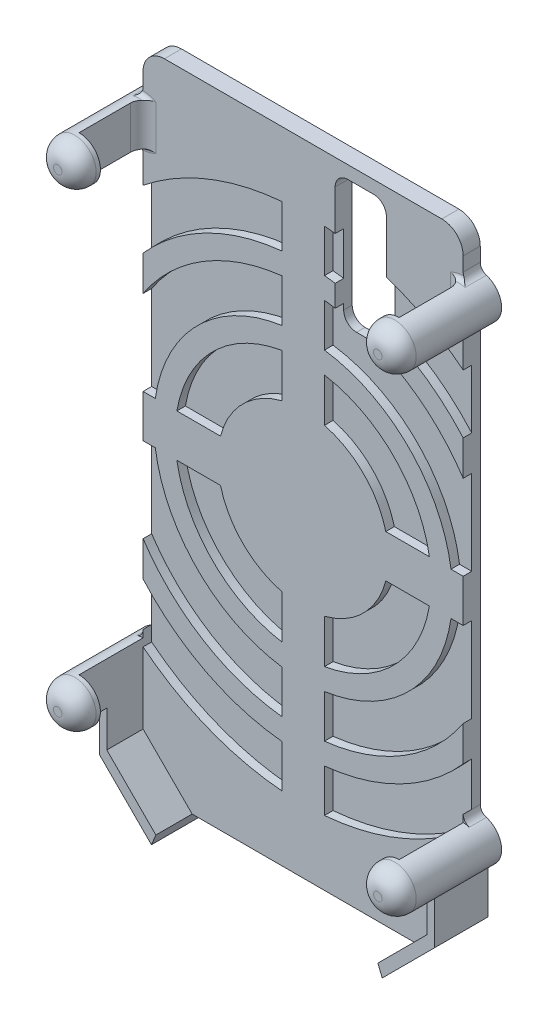
SolidWorks part; units mm, degrees
ref_plane "Front Plane" through (0, 0, 0) normal (0, 0, 1) x (1, 0, 0)
ref_plane "Top Plane" through (0, 0, 0) normal (0, 1, 0) x (1, 0, 0)
ref_plane "Right Plane" through (0, 0, 0) normal (1, 0, 0) x (0, 0, -1)
sketch "Sketch1" plane through (0, 0, 0) normal (0, 0, 1) x (1, 0, 0)
  line L0 (-925, 75) -> (49075, 75) construction
  line L1 (11.5, 0) -> (63.5, 0)
  line L2 (0, 11.5) -> (0, 20)
  line L3 (0, 150) -> (75, 150)
  line L4 (75, 11.5) -> (75, 20)
  line L5 (37.5, -1000) -> (37.5, 49000) construction
  line L6 (63.5, -1000) -> (63.5, 49000) construction
  line L7 (11.5, -1000) -> (11.5, 49000) construction
  line L8 (-643.6068, -707.1068) -> (34711.7323, 34648.2323) construction
  line L9 (718.6068, -707.1068) -> (-34636.7323, 34648.2323) construction
  line L10 (63.5, 0) -> (75, 11.5)
  line L11 (11.5, 0) -> (0, 11.5)
  line L12 (75, 140) -> (75, 150)
  line L13 (0, 140) -> (0, 150)
  line L14 (0, 30) -> (0, 130)
  line L15 (75, 30) -> (75, 130)
  line L16 (64.5355, -2.5) -> (76.7678, 9.7322)
  line L18 (10.4645, -2.5) -> (-1.7678, 9.7322)
  line L19 (-1.7678, 9.7322) -> (-1.7678, 20.3229)
  line L20 (76.7678, 9.7322) -> (76.7678, 20.3229)
  line L21 (11.5, 0) -> (10.4645, -2.5)
  line L22 (63.5, 0) -> (64.5355, -2.5)
  line L24 (10.4645, -2.5) -> (64.5355, -2.5) construction
  circle A0 centre (0, 135) radius 5
  circle A1 centre (75, 135) radius 5
  circle A2 centre (75, 25) radius 5
  circle A3 centre (0, 25) radius 5
  dimension "D5" = 25
  dimension "D7" = 15
  dimension "D1" = 2.5
  dimension "D2" = 130
  dimension "D3" = 26
  dimension "D4" = 26
  dimension "D6" = 25
extrude "Boss-Extrude1" add sketch "Sketch1" along normal blind 4 contours L14 A3 L2 L11 L1 L10 L4 A2 L15 A1 L12 L3 L13 A0 region at (37.5, 75.787, 0)
extrude "Boss-Extrude2" add sketch "Sketch1<3>" along normal blind 24 contours A3 | A0 | A1 | A2 region at (0, 25, 0) region at (75, 25, 0) region at (75, 135, 0) region at (0, 135, 0)
sketch "Sketch1<3>" plane through (0, 0, 0) normal (0, 0, 1) x (1, 0, 0) same geometry as "Sketch1"
extrude "Boss-Extrude3" add sketch "Sketch1<4>" along normal blind 12.5 contours L2 A3 L19 L18 L16 L20 A2 L4 L10 L1 L11 | L2 A3 L19 L18 L21 L11 region at (3.34, 7.7217, 0) region at (71.66, 7.7217, 0)
sketch "Sketch1<4>" plane through (0, 0, 0) normal (0, 0, 1) x (1, 0, 0) same geometry as "Sketch1"
ref_plane "Plane1" through (0, 150, 0) normal (0, 1, 0) x (1, 0, 0)
sketch "Sketch2" plane through (0, 150, 0) normal (0, 1, 0) x (1, 0, 0)
  line L1 (75, -4) -> (0, -4)
  line L2 (75, -4) -> (75, -19)
  line L3 (75, -19) -> (0, -19)
  line L4 (0, -4) -> (0, -19)
  dimension "D1" = 15
  dimension "D2" = 75
extrude "Cut-Extrude1" cut sketch "Sketch2" against normal blind 130
fillet "Fillet1" radius 4 4 edges at (80, 25, 24) (5, 25, 24) (5, 135, 24) (80, 135, 24)
fillet "Fillet2" radius 5 2 edges at (0, 150, 2) (75, 150, 2)
fillet "Fillet3" radius 2 6 edges at (75, 30, 2) (0, 30, 2) (0, 130, 2) (0, 140, 2) (75, 130, 2) (75, 140, 2)
ref_plane "Plane2" through (0, 0, 0) normal (0, 0, -1) x (-1, 0, 0)
sketch "Sketch3" plane through (0, 0, 0) normal (0, 0, -1) x (-1, 0, 0)
  line L0 (-45, -884.4947) -> (-45, 49115.5053) construction
  line L1 (-57, -886.6069) -> (-57, 49113.3931) construction
  line L2 (-1043.6831, 115) -> (48956.3169, 115) construction
  line L4 (14.1321, 150) -> (-14.1321, 150) construction
  line L5 (-1041.9112, 147) -> (48958.0888, 147) construction
  line L6 (-75, 31.7082) -> (-75, 128.2918) construction
  line L7 (-54, 147) -> (-48, 147)
  line L8 (-57, 144) -> (-57, 118)
  line L9 (-54, 115) -> (-48, 115)
  line L10 (-45, 144) -> (-45, 118)
  arc A0 (-48, 147) -> (-45, 144) centre (-48, 144) cw
  arc A1 (-54, 147) -> (-57, 144) centre (-54, 144) ccw
  arc A2 (-54, 115) -> (-57, 118) centre (-54, 118) cw
  arc A3 (-48, 115) -> (-45, 118) centre (-48, 118) ccw
  point P20 (-57, 147)
  point P25 (-45, 115)
  dimension "D5" = 3
  dimension "D1" = 18
  dimension "D2" = 12
  dimension "D3" = 35
  dimension "D4" = 3
extrude "Cut-Extrude3" cut sketch "Sketch3" against normal through all
ref_plane "Plane3" through (0, 0, 4) normal (0, 0, 1) x (1, 0, 0)
sketch "Sketch5" plane through (0, 0, 4) normal (0, 0, 1) x (1, 0, 0)
  line L0 (37.5, -945.5831) -> (37.5, 49054.4169) construction
  line L1 (-967.7787, 75) -> (49032.2213, 75) construction
  line L2 (5, 150) -> (70, 150) construction
  line L3 (75, 31.7082) -> (75, 128.2918) construction
  line L4 (0, 31.7082) -> (0, 128.2918) construction
  line L6 (0, 80) -> (75, 80)
  line L7 (0, 80) -> (0, 70)
  line L8 (0, 70) -> (75, 70)
  line L9 (75, 80) -> (75, 70)
  line L10 (32.5, 150) -> (42.5, 150)
  line L11 (32.5, 150) -> (32.5, 0)
  line L12 (42.5, 150) -> (42.5, 0)
  line L13 (11.5, 0) -> (63.5, 0) construction
  line L14 (0, -913.4991) -> (0, 49086.5009)
  line L16 (75, -946.3581) -> (75, 49053.6419)
  line L20 (42.5, 0) -> (32.5, 0)
  arc A0 (32.5, 89.1421) -> (32.5, 60.8579) centre (37.5, 75) ccw
  arc A1 (32.5, 94.3649) -> (32.5, 55.6351) centre (37.5, 75) ccw
  arc A2 (32.5, 104.5804) -> (32.5, 45.4196) centre (37.5, 75) ccw
  arc A3 (32.5, 109.641) -> (32.5, 40.359) centre (37.5, 75) ccw
  arc A4 (0, 50.1253) -> (32.5, 30.2786) centre (37.5, 75) ccw
  arc A5 (0, 41.9281) -> (32.5, 25.2506) centre (37.5, 75) ccw
  arc A6 (0, 28.1625) -> (32.5, 15.2087) centre (37.5, 75) ccw
  arc A7 (0, 21.9081) -> (32.5, 10.1926) centre (37.5, 75) ccw
  arc A8 (75, 128.0919) -> (42.5, 139.8074) centre (37.5, 75) ccw
  arc A9 (75, 121.8375) -> (42.5, 134.7913) centre (37.5, 75) ccw
  arc A10 (75, 108.0719) -> (37.5, 125) centre (37.5, 75) ccw
  arc A11 (75, 99.8747) -> (37.5, 120) centre (37.5, 75) ccw
  arc A12 (32.5, 139.8074) -> (30, 139.5659) centre (37.5, 75) ccw
  arc A16 (42.5, 60.8579) -> (42.5, 89.1421) centre (37.5, 75) ccw
  arc A17 (42.5, 55.6351) -> (42.5, 94.3649) centre (37.5, 75) ccw
  arc A18 (42.5, 45.4196) -> (42.5, 104.5804) centre (37.5, 75) ccw
  arc A19 (42.5, 40.359) -> (42.5, 109.641) centre (37.5, 75) ccw
  arc A20 (42.5, 30.2786) -> (75, 50.1253) centre (37.5, 75) ccw
  arc A21 (42.5, 25.2506) -> (75, 41.9281) centre (37.5, 75) ccw
  arc A22 (42.5, 15.2087) -> (75, 28.1625) centre (37.5, 75) ccw
  arc A23 (42.5, 10.1926) -> (75, 21.9081) centre (37.5, 75) ccw
  arc A24 (32.5, 134.7913) -> (0, 121.8375) centre (37.5, 75) ccw
  arc A25 (30, 139.5659) -> (0, 128.0919) centre (37.5, 75) ccw
  arc A26 (32.5, 124.7494) -> (0, 108.0719) centre (37.5, 75) ccw
  arc A27 (32.5, 119.7214) -> (0, 99.8747) centre (37.5, 75) ccw
  dimension "D2" = 37.5
  dimension "D3" = 10
extrude "Cut-Extrude4" cut sketch "Sketch5" against normal blind 2 contours A26 L11 A24 L14 | A10 L16 A9 L12 | A19 L6 L16 A11 L12 | L11 A27 L14 L6 A3 | L6 A18 L12 A17 | L11 A2 L6 A1 | L8 A2 L11 A1 | L12 A20 L16 L8 A19 | L12 A18 L8 A17 | L14 A4 L11 A3 L8 | L14 A6 L11 A5 | L12 A22 L16 A21 region at (13.8879, 104.316, 4) region at (13.8879, 45.684, 4) region at (20.5234, 91.9766, 4) region at (15.4302, 124.2161, 4) region at (20.5234, 58.0234, 4) region at (15.4302, 25.7839, 4) region at (54.4766, 91.9766, 4) region at (54.4766, 58.0234, 4) region at (59.5698, 124.2161, 4) region at (61.1121, 104.316, 4) region at (59.5698, 25.7839, 4) region at (61.1121, 45.684, 4)
sketch "magnetHoles" plane through (0, 0, 0) normal (0, 0, -1) x (-1, 0, 0)
  line L0 (-1034.1381, 75) -> (48965.8619, 75) construction
  line L1 (-37.5, -938.7688) -> (-37.5, 49061.2312) construction
  line L2 (0, 31.7082) -> (0, 128.2918) construction
  line L3 (-11.5, 0) -> (-63.5, 0) construction
  circle A0 centre (-24.8, 75) radius 5.2
  circle A1 centre (-37.5, 87.7) radius 5.2
  circle A2 centre (-37.5, 62.3) radius 5.2
  circle A3 centre (-50.2, 75) radius 5.2
  point P19 (-37.5, 75)
  dimension "D3" = 12.7
  dimension "D1" = 37.5
  dimension "D2" = 75
  dimension "D4" = 4
fillet "Fillet4" radius 3 2 edges at (0, 135, 4) (75, 135, 4)
fillet "Fillet5" radius 1 4 edges at (74.1202, 139.922, 4) (74.1202, 130.078, 4) (0.8798, 130.078, 4) (0.8798, 139.922, 4)
extrude "Cut-Extrude5" cut sketch "magnetHoles" against normal blind 3
